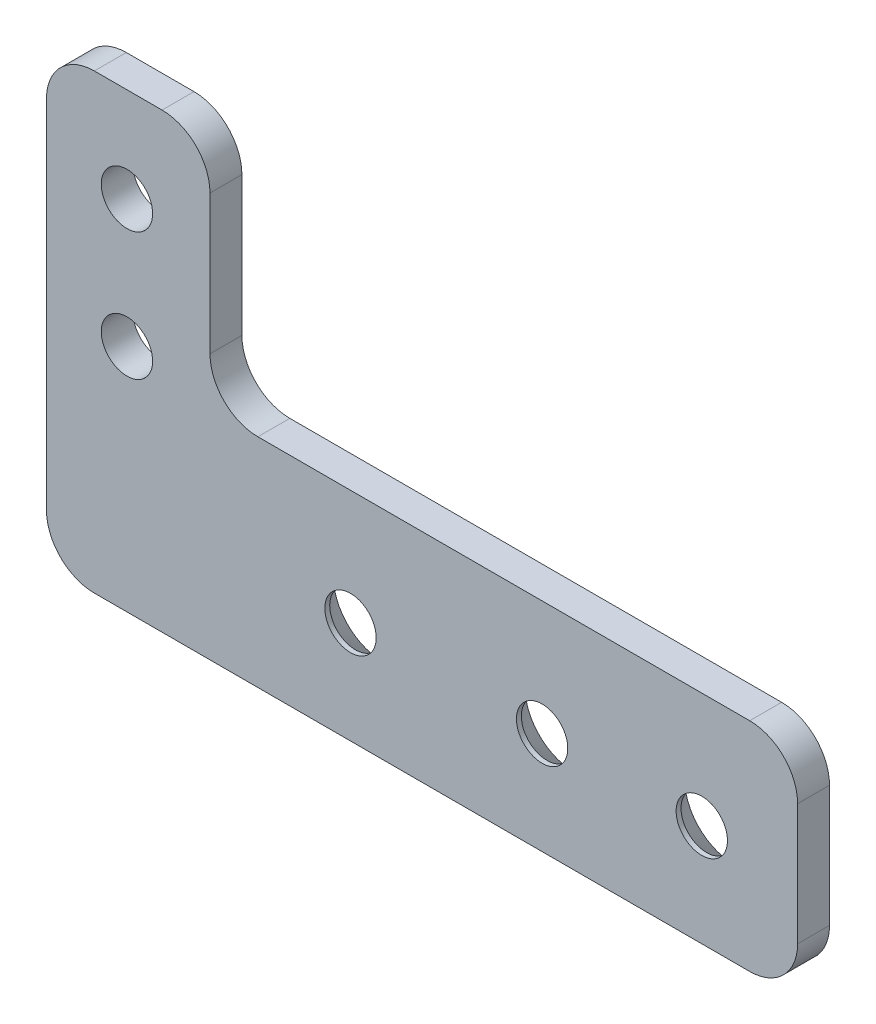
SolidWorks part; units mm, degrees
material "6061-T6 (SS)"
ref_plane "Front Plane" through (0, 0, 0) normal (0, 0, 1) x (1, 0, 0)
ref_plane "Top Plane" through (0, 0, 0) normal (0, 1, 0) x (1, 0, 0)
ref_plane "Right Plane" through (0, 0, 0) normal (1, 0, 0) x (0, 0, -1)
sketch "Sketch1" plane through (0, 0, 0) normal (0, 0, 1) x (1, 0, 0)
  line L0 (41.275, -11.049) -> (-33.401, -11.049) construction
  line L1 (-41.275, -23.749) -> (41.275, -23.749)
  line L2 (-41.275, -23.749) -> (-41.275, 23.749)
  line L3 (-41.275, 23.749) -> (41.275, 23.749)
  line L4 (41.275, -23.749) -> (41.275, 23.749)
  line L5 (-41.275, -23.749) -> (41.275, 23.749) construction
  line L6 (-41.275, 23.749) -> (41.275, -23.749) construction
  line L7 (41.275, 23.749) -> (-17.145, 23.749)
  line L8 (41.275, 23.749) -> (41.275, 0.381)
  line L9 (41.275, 0.381) -> (-17.145, 0.381)
  line L10 (-17.145, 23.749) -> (-17.145, 0.381)
  line L11 (-41.275, -23.749) -> (-33.401, -23.749)
  line L12 (-41.275, -23.749) -> (-41.275, 23.749)
  line L13 (-41.275, 23.749) -> (-33.401, 23.749)
  line L14 (-33.401, -23.749) -> (-33.401, 23.749)
  line L15 (-33.401, -23.749) -> (41.275, -23.749)
  line L16 (-33.401, -23.749) -> (-33.401, -21.209)
  line L17 (-33.401, -21.209) -> (41.275, -21.209)
  line L18 (41.275, -23.749) -> (41.275, -21.209)
  line L19 (-33.401, 23.876) -> (-17.145, 23.876) construction
  circle A0 centre (-25.4, -11.049) radius 2.5527
  circle A1 centre (-25.4, 1.651) radius 2.5527
  circle A2 centre (-25.4, 14.351) radius 2.5527
  point P0 (0, 0)
  point P22 (31.75, -11.049)
  point P23 (-3.175, -11.049)
  point P24 (15.875, -11.049)
  dimension "D7" = 5.1054
  dimension "D1" = 82.55
  dimension "D2" = 47.498
  dimension "D3" = 24.13
  dimension "D4" = 24.13
  dimension "D5" = 7.874
  dimension "D6" = 47.498
  dimension "D8" = 22.225
  dimension "D9" = 12.7
  dimension "D10" = 12.7
  dimension "D11" = 12.7
  dimension "D12" = 9.525
  dimension "D13" = 57.15
  dimension "D14" = 15.875
  dimension "D15" = 15.875
  dimension "D16" = 2.54
extrude "Boss-Extrude1" add sketch "Sketch1" along normal blind 3.175 contours L14 L17 L4 L9 L10 L3 A2 A1 A0 | A0 region at (-0.8769, -6.375, 0) region at (-25.4, -11.049, 0)
fillet "Fillet1" radius 4.7625 6 edges at (-33.401, 23.749, 1.5875) (-17.145, 23.749, 1.5875) (-17.145, 0.381, 1.5875) (41.275, 0.381, 1.5875) (41.275, -21.209, 1.5875) (-33.401, -21.209, 1.5875)
hole_wizard "CSK for #10 Flat Head Machine Screw3" positions "Sketch6" profile "Sketch7" countersink size "#10" standard "ANSI Inch" end condition through all
sketch "Sketch6" plane through (0, 0, 0) normal (0, 0, -1) x (-1, 0, 0)
  point P0 (-31.75, -11.049)
  point P3 (-15.875, -11.049)
  point P6 (3.175, -11.049)
sketch "Sketch7" plane through (31.75, -11.049, 0) normal (1, 0, 0) x (0, 1, 0)
  line L0 (0, 0) -> (0, 3.175)
  line L1 (0, 3.175) -> (2.5527, 3.175)
  line L2 (2.5527, 3.175) -> (2.5527, 2.6882)
  line L3 (2.5527, 2.6882) -> (4.8895, 0)
  line L5 (4.8895, 0) -> (0, 0)
  line L6 (-2.5527, 2.6882) -> (-4.8895, 0) construction
  line L11 (0, -6.35) -> (0, 107.95) construction
  dimension "Thru Hole Dia." = 5.1054
  dimension "Thru Hole Depth" = 3.175
  dimension "Near C'Sink Dia." = 9.779
  dimension "Near C'Sink Angle" = 82
